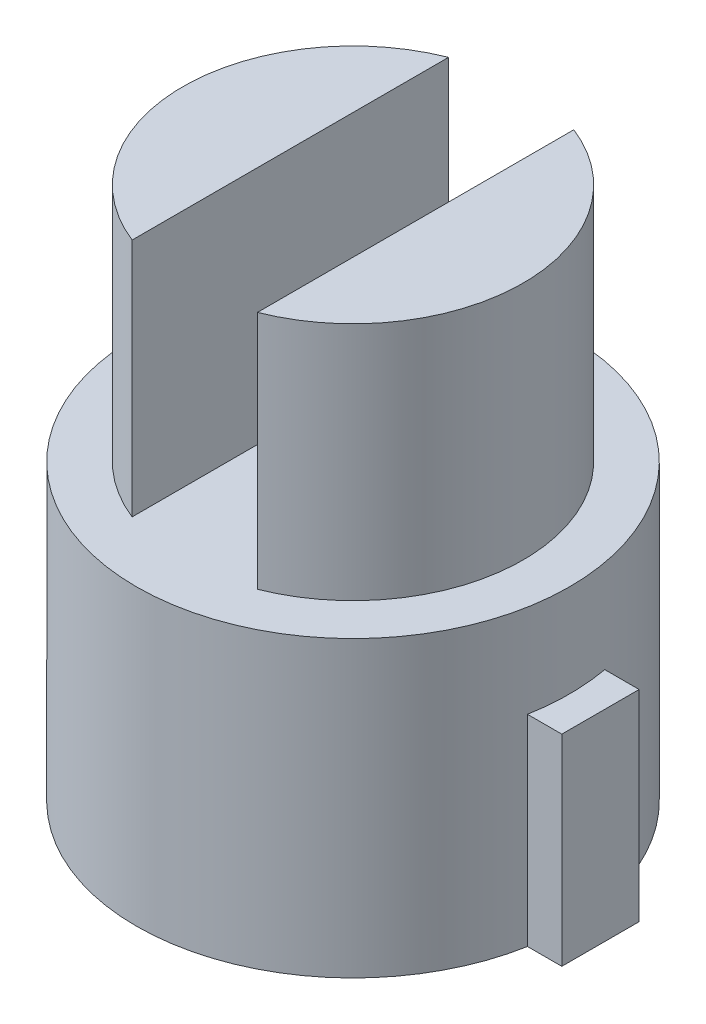
SolidWorks part; units mm, degrees
ref_plane "前视基准面" through (0, 0, 0) normal (0, 0, 1) x (1, 0, 0)
ref_plane "上视基准面" through (0, 0, 0) normal (0, 1, 0) x (1, 0, 0)
ref_plane "右视基准面" through (0, 0, 0) normal (1, 0, 0) x (0, 0, -1)
other "Configuration Table"
sketch "Sketch1" plane through (0, 0, 0) normal (0, 1, 0) x (1, 0, 0)
  line L2 (-4.0485, -10.2142) -> (-4.0532, -10.226)
  line L3 (0, -2.4982) -> (15.9953, -2.4982)
  line L5 (0, 2.5) -> (15.9953, 2.5)
  line L6 (15.9953, -2.4982) -> (15.9953, 2.5)
  line L7 (0, -2.4982) -> (-16, -2.4982)
  line L9 (0, 2.5018) -> (-16, 2.5018)
  line L10 (-16, -2.4982) -> (-16, 2.5018)
  line L21 (-4.0509, 10.227) -> (-4.0509, -10.227)
  line L23 (4.0509, 10.227) -> (4.0509, -10.227)
  circle A0 centre (0, 0) radius 11
  circle A1 centre (0, 0) radius 14
  dimension "D1" = 4.9982
  dimension "D2" = 15.9953
  dimension "D3" = 5
  dimension "D4" = 16
  dimension "D5" = 20.4539
  dimension "D6" = 8.1017
extrude "Boss-Extrude1" add sketch "Sketch1" along normal blind 34.5 contours L7 A0 L2 | L9 A0 L7 | A0 L9 | L5 A0 | L3 A0 L5 | A0 L3 region at (-6.6463, 0, 5.4808) region at (-7.4782, 0, -0.0017) region at (-6.6458, 0, -5.4828) region at (6.6463, 0, 5.4808) region at (7.4783, 0, -0.0009) region at (6.6461, 0, -5.4818)
extrude "Boss-Extrude2" add sketch "Sketch1<4>" along normal blind 19 contours L5 A1 L9 A0 | L9 A1 L7 A0 | L7 A1 L3 A0 | L3 A1 L5 A0 | L23 A0 L21 L7 L3 | L21 A0 L23 L3 L7 region at (0, 0, 6.6253) region at (-4.162, 0, 10.504) region at (0, 0, -4.1259) region at (-12.4144, 0, -0.0018) region at (-12.2432, 0, -2.8003) region at (12.4145, 0, -0.0009)
sketch "Sketch1<4>" plane through (0, 0, 0) normal (0, 1, 0) x (1, 0, 0) same geometry as "Sketch1"
extrude "Boss-Extrude3" add sketch "Sketch1<5>" along normal blind 13 contours A1 L9 L10 L7 | A1 L3 L6 L5 region at (-14.9615, 0, -0.0019) region at (14.9592, 0, -0.0009)
sketch "Sketch1<5>" plane through (0, 0, 0) normal (0, 1, 0) x (1, 0, 0) same geometry as "Sketch1"
